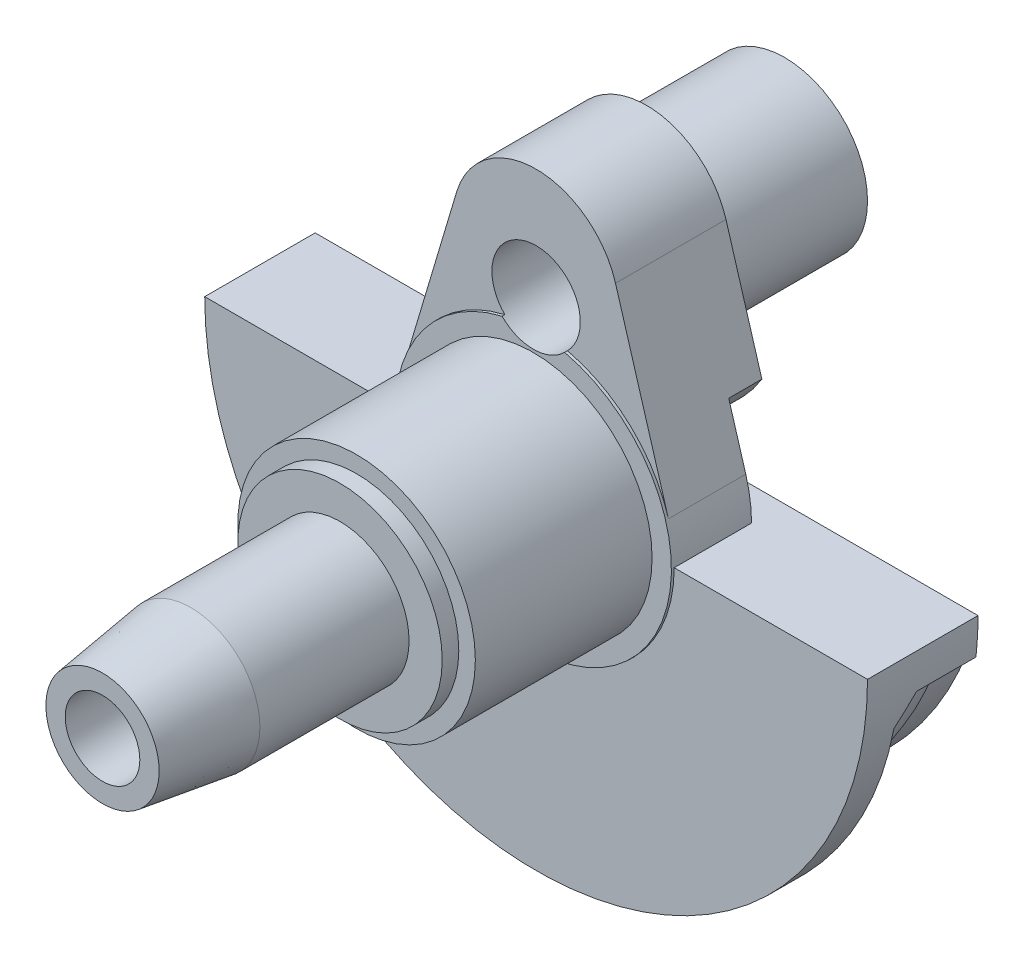
SolidWorks part; units mm, degrees
ref_plane "Front Plane" through (0, 0, 0) normal (0, 0, 1) x (1, 0, 0)
ref_plane "Top Plane" through (0, 0, 0) normal (0, 1, 0) x (1, 0, 0)
ref_plane "Right Plane" through (0, 0, 0) normal (1, 0, 0) x (0, 0, -1)
sketch "Sketch1" plane through (0, 0, 0) normal (0, 0, 1) x (1, 0, 0)
  line L0 (0, 0) -> (0, 70) construction
  line L1 (-28.7494, 78.5714) -> (-47.9157, 14.2857)
  line L2 (28.7494, 78.5714) -> (47.9157, 14.2857)
  line L3 (-41.7399, 35) -> (41.7399, 35) construction
  line L4 (-120, 0) -> (-50, 0)
  line L5 (120, 0) -> (50, 0)
  circle A0 centre (0, 0) radius 50
  arc A1 (-28.7494, 78.5714) -> (28.7494, 78.5714) centre (0, 70) cw
  arc A2 (120, 0) -> (-120, 0) centre (0, 0) cw
  point P10 (0, 35)
  dimension "D1" = 100
  dimension "D2" = 30
  dimension "D4" = 120
  dimension "D3" = 70
extrude "Boss-Extrude1" add sketch "Sketch1" along normal blind 1 and the other way blind 40 contours A0 region at (0, 0, 0)
extrude "Boss-Extrude2" add sketch "Sketch1<3>" against normal up to surface (40 mm away) contours A2 L5 A0 L4 | A1 L1 A0 L2 region at (0, 66.8029, 0) region at (0, -57.171, 0) up to face at (50, 0, -40)
sketch "Sketch1<3>" plane through (0, 0, 0) normal (0, 0, 1) x (1, 0, 0) same geometry as "Sketch1"
sketch "Sketch2" plane through (0, 0, 0) normal (1, 0, 0) x (0, 0, -1)
  line L0 (-1, 0) -> (-1, 43)
  line L1 (-1, 50) -> (-1, -50) construction
  line L2 (-1, 43) -> (-65, 43)
  line L3 (-65, 43) -> (-65, 37)
  line L4 (-65, 37) -> (-71, 37)
  line L5 (-71, 37) -> (-71, 25)
  line L6 (-71, 25) -> (-125, 25)
  line L7 (-125, 25) -> (-125, 0)
  line L8 (-125, 0) -> (-1, 0)
  dimension "D1" = 43
  dimension "D2" = 64
  dimension "D3" = 6
  dimension "D4" = 12
  dimension "D5" = 54
revolve "Revolve1" add sketch "Sketch2" angle 360 about L8
sketch "Sketch3" plane through (0, 0, 125) normal (0, 0, 1) x (1, 0, 0)
  circle A1 centre (0, 0) radius 25
  circle A2 centre (0, 0) radius 25
  dimension "D1" = 0
extrude "Boss-Extrude3" add sketch "Sketch3" along normal blind 32 draft 8
sketch "Sketch4" plane through (0, 0, -40) normal (0, 0, -1) x (-1, 0, 0)
  circle A0 centre (0, 60) radius 30
  arc A2 (28.7494, 78.5714) -> (-28.7494, 78.5714) centre (0, 70) ccw construction
  dimension "D1" = 60
extrude "Boss-Extrude4" add sketch "Sketch4" along normal blind 50
sketch "Sketch5" plane through (0, 0, -90) normal (0, 0, -1) x (-1, 0, 0)
  circle A2 centre (0, 60) radius 21
  circle A3 centre (0, 60) radius 21
  dimension "D1" = 9
extrude "Cut-Extrude1" cut sketch "Sketch5" against normal blind 25
sketch "Sketch6" plane through (0, 0, -65) normal (0, 0, -1) x (-1, 0, 0)
  circle A2 centre (0, 60) radius 11
  circle A3 centre (0, 60) radius 11
  dimension "D1" = 10
extrude "Cut-Extrude2" cut sketch "Sketch6" against normal up to surface (66 mm away) up to face at (50, 0, 1)
sketch "Sketch7" plane through (0, 0, -40) normal (0, 0, -1) x (-1, 0, 0)
  circle A2 centre (0, 60) radius 16
  circle A3 centre (0, 60) radius 16
  dimension "D1" = 5
extrude "Cut-Extrude3" cut sketch "Sketch7" against normal up to surface (41 mm away) up to face at (0, -0.5, 1)
sketch "Sketch8" plane through (0, 0, 157) normal (0, 0, 1) x (1, 0, 0)
  circle A2 centre (0, 0) radius 13.5027
  circle A3 centre (0, 0) radius 13.5027
  dimension "D1" = 7
extrude "Cut-Extrude4" cut sketch "Sketch8" against normal blind 30
sketch "Sketch9" plane through (0, 0, 0) normal (1, 0, 0) x (0, 0, -1)
  line L0 (40, -120) -> (40, -94)
  line L1 (40, -120) -> (40, 0) construction
  line L2 (40, -94) -> (28, -94)
  line L3 (28, -94) -> (11.6457, -99)
  line L4 (11.6457, -99) -> (11.6457, -120)
  line L5 (0, -120) -> (40, -120) construction
  line L6 (11.6457, -120) -> (40, -120)
  line L7 (40, 30) -> (90, 30) construction
  line L8 (40, 30) -> (90, 30) construction
  dimension "D1" = 12
  dimension "D2" = 21
  dimension "D3" = 26
  dimension "D4" = 107
revolve "Cut-Revolve1" cut sketch "Sketch9" angle 140 mid plane about L8
sketch "Sketch10" plane through (0, 0, -40) normal (0, 0, -1) x (-1, 0, 0)
  line L0 (-28.7494, 78.5714) -> (-47.9157, 14.2857) construction
  line L1 (28.7494, 78.5714) -> (47.9157, 14.2857) construction
  line L2 (-41.7399, 35) -> (-47.9157, 14.2857)
  line L3 (41.7399, 35) -> (47.9157, 14.2857)
  line L4 (-50, 0) -> (50, 0)
  arc A0 (-41.7399, 35) -> (41.7399, 35) centre (0, 60) ccw
  circle A1 centre (0, 60) radius 30 construction
  circle A2 centre (0, 0) radius 50 construction
  arc A3 (-47.9157, 14.2857) -> (-50, 0) centre (0, 0) ccw
  arc A4 (50, 0) -> (47.9157, 14.2857) centre (0, 0) ccw
extrude "Cut-Extrude5" cut sketch "Sketch10" against normal up to vertex (12 mm away) up to point (116.5219, -12.4105, -28)
equation "\"D2@Sketch1\"=\"D1@Sketch1\"*.3"
equation "\"D3@Sketch1\"=\"D1@Sketch1\"*.7"
equation "\"D4@Sketch1\"=\"D1@Sketch1\"*1.2"
equation "\"D1@Boss-Extrude1\"=\"D1@Sketch1\"*.01"
equation "\"D2@Boss-Extrude1\"=\"D1@Sketch1\"*.4"
